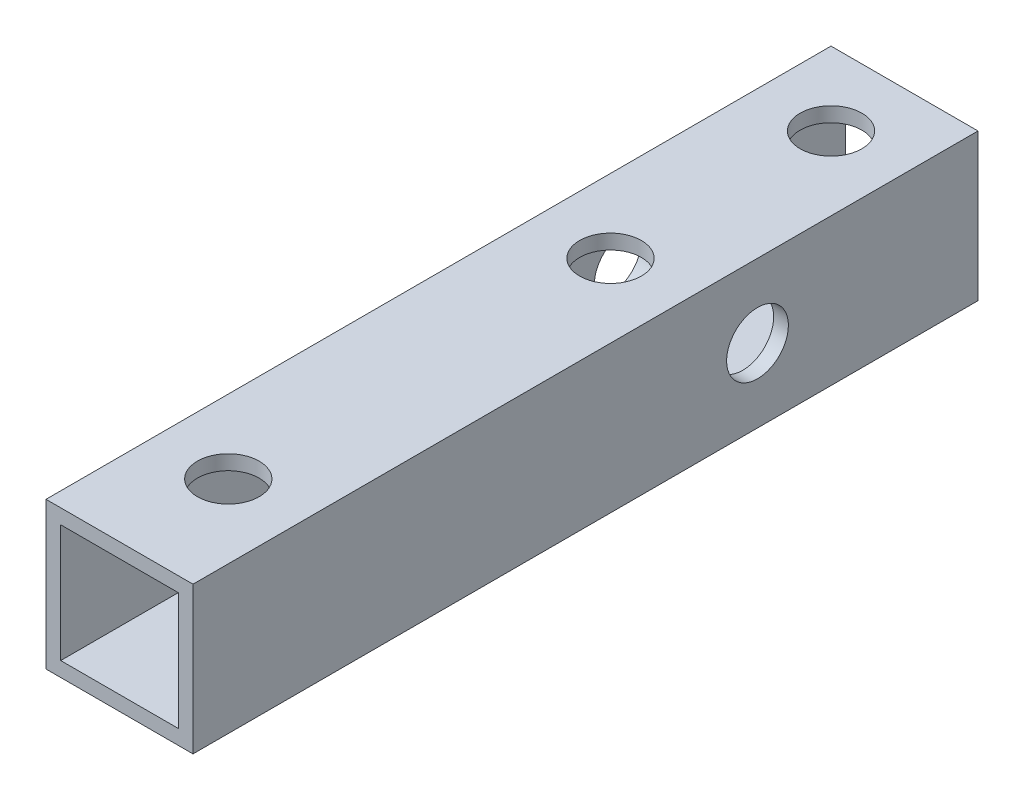
SolidWorks part; units mm, degrees
material "5052-H34"
ref_plane "正面" through (0, 0, 0) normal (0, 0, 1) x (1, 0, 0)
ref_plane "平面" through (0, 0, 0) normal (0, 1, 0) x (1, 0, 0)
ref_plane "右側面" through (0, 0, 0) normal (1, 0, 0) x (0, 0, -1)
sketch "ｽｹｯﾁ1" plane through (0, 0, 0) normal (0, 0, 1) x (1, 0, 0)
  line L1 (-5, 5) -> (5, 5)
  line L2 (-5, 5) -> (-5, -5)
  line L3 (-5, -5) -> (5, -5)
  line L4 (5, 5) -> (5, -5)
  line L5 (-5, 5) -> (5, -5) construction
  line L6 (-5, -5) -> (5, 5) construction
  point P0 (0, 0)
  dimension "D1" = 10
  dimension "D2" = 10
extrude "押し出し-薄板1" add sketch "ｽｹｯﾁ1" along normal blind 53.4 thin thin type one direction reverse wall 1
sketch "ｽｹｯﾁ2" plane through (5, 0, 0) normal (1, 0, 0) x (0, 0, -1)
  line L0 (0, 0) -> (-15, 0) construction
  line L1 (0, -5) -> (0, 5) construction
  circle A0 centre (-15, 0) radius 2.1
  dimension "D1" = 4.2
  dimension "D2" = 15
extrude "ｶｯﾄ - 押し出し1" cut sketch "ｽｹｯﾁ2" against normal through all
sketch "ｽｹｯﾁ3" plane through (0, 5, 0) normal (0, 1, 0) x (1, 0, 0)
  line L0 (0, 0) -> (0, -5) construction
  line L1 (0, -53.4) -> (0, -20) construction
  line L2 (5, -53.4) -> (-5, -53.4) construction
  line L3 (5, 0) -> (-5, 0) construction
  circle A0 centre (0, -5) radius 2.1
  circle A1 centre (0, -20) radius 2.1
  circle A2 centre (0, -46) radius 2.1
  dimension "D1" = 4.2
  dimension "D3" = 4.2
  dimension "D2" = 5
  dimension "D4" = 7.4
  dimension "D5" = 26
extrude "ｶｯﾄ - 押し出し2" cut sketch "ｽｹｯﾁ3" against normal through all
